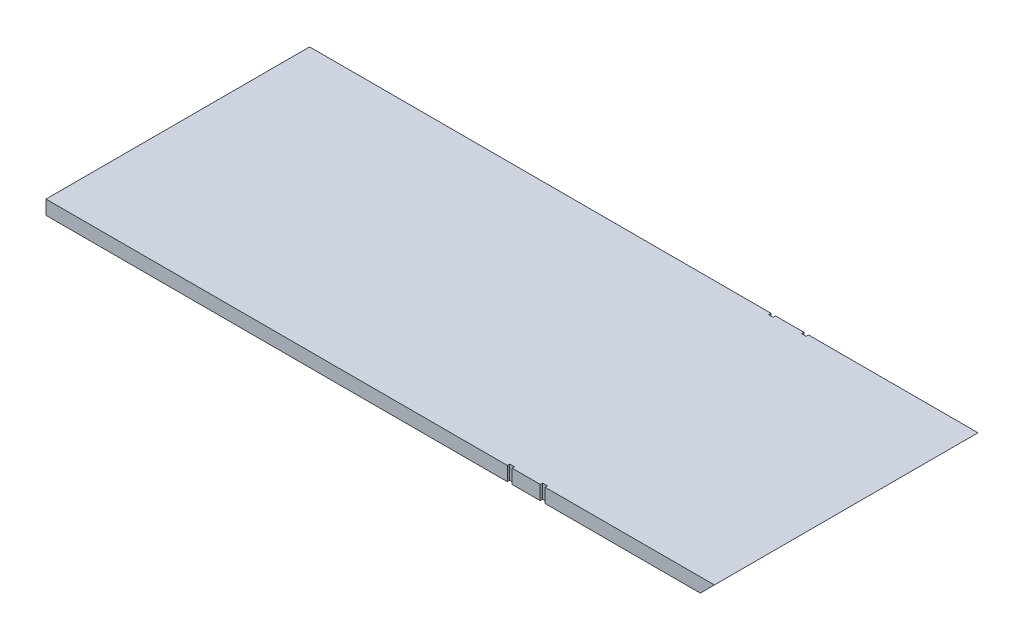
SolidWorks part; units mm, degrees
ref_plane "Front Plane" through (0, 0, 0) normal (0, 0, 1) x (1, 0, 0)
ref_plane "Top Plane" through (0, 0, 0) normal (0, 1, 0) x (1, 0, 0)
ref_plane "Right Plane" through (0, 0, 0) normal (1, 0, 0) x (0, 0, -1)
sketch "Sketch1" plane through (0, 0, 0) normal (0, 1, 0) x (1, 0, 0)
  line L1 (450.85, 177.8) -> (-450.85, 177.8)
  line L2 (450.85, 177.8) -> (450.85, -177.8)
  line L3 (450.85, -177.8) -> (-450.85, -177.8)
  line L4 (-450.85, 177.8) -> (-450.85, -177.8)
  line L5 (450.85, 177.8) -> (-450.85, -177.8) construction
  line L6 (450.85, -177.8) -> (-450.85, 177.8) construction
  point P0 (0, 0)
  dimension "D1" = 355.6
  dimension "D2" = 901.7
extrude "Boss-Extrude1" add sketch "Sketch1" along normal mid plane 19.05
chamfer "Chamfer1" distance 19.05 angle 45 1 edges at (450.85, -9.525, 0)
sketch "Sketch2" plane through (0, 0, 177.8) normal (0, 0, 1) x (1, 0, 0)
  line L0 (177.8, 9.525) -> (171.45, 9.525) construction
  line L1 (222.25, 9.525) -> (215.9, 9.525) construction
  line L2 (171.45, 9.525) -> (171.45, -142.875) construction
  line L3 (177.8, 9.525) -> (177.8, -142.875) construction
  line L4 (215.9, -142.875) -> (215.9, 9.525) construction
  line L5 (222.25, -142.875) -> (222.25, 9.525) construction
  line L6 (177.8, 9.525) -> (171.45, 9.525)
  line L7 (222.25, 9.525) -> (215.9, 9.525)
  line L8 (171.45, 9.525) -> (171.45, -9.525)
  line L9 (177.8, 9.525) -> (177.8, -9.525)
  line L10 (215.9, -9.525) -> (215.9, 9.525)
  line L11 (222.25, -9.525) -> (222.25, 9.525)
  line L12 (222.25, -9.525) -> (215.9, -9.525)
  line L13 (-450.85, -9.525) -> (431.8, -9.525) construction
  line L14 (177.8, -9.525) -> (171.45, -9.525)
extrude "Cut-Extrude1" cut sketch "Sketch2" against normal blind 3.175
sketch "Sketch3" plane through (0, 0, -177.8) normal (0, 0, -1) x (-1, 0, 0)
  line L0 (-177.8, 9.525) -> (-171.45, 9.525) construction
  line L1 (-222.25, 9.525) -> (-215.9, 9.525) construction
  line L2 (-171.45, -142.875) -> (-171.45, 9.525) construction
  line L3 (-177.8, -142.875) -> (-177.8, 9.525) construction
  line L4 (-215.9, 9.525) -> (-215.9, -142.875) construction
  line L5 (-222.25, 9.525) -> (-222.25, -142.875) construction
  line L6 (-177.8, 9.525) -> (-171.45, 9.525)
  line L7 (-222.25, 9.525) -> (-215.9, 9.525)
  line L8 (-171.45, -9.525) -> (-171.45, 9.525)
  line L9 (-177.8, -9.525) -> (-177.8, 9.525)
  line L10 (-215.9, 9.525) -> (-215.9, -9.525)
  line L11 (-222.25, 9.525) -> (-222.25, -9.525)
  line L12 (-222.25, -9.525) -> (-215.9, -9.525)
  line L13 (-431.8, -9.525) -> (450.85, -9.525) construction
  line L14 (-177.8, -9.525) -> (-171.45, -9.525)
extrude "Cut-Extrude2" cut sketch "Sketch3" against normal blind 3.175
